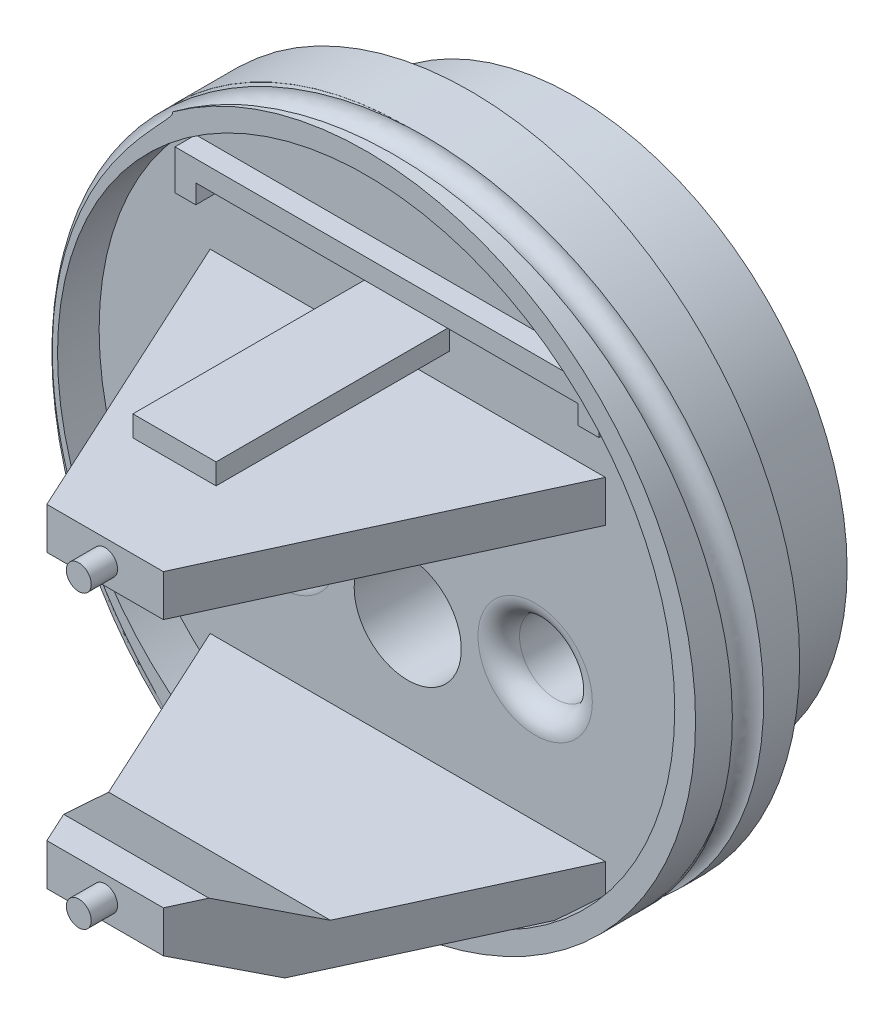
SolidWorks part; units mm, degrees
ref_plane "Front Plane" through (0, 0, 0) normal (0, 0, 1) x (1, 0, 0)
ref_plane "Top Plane" through (0, 0, 0) normal (0, 1, 0) x (1, 0, 0)
ref_plane "Right Plane" through (0, 0, 0) normal (1, 0, 0) x (0, 0, -1)
sketch "Sketch1" plane through (0, 0, 0) normal (0, 0, 1) x (1, 0, 0)
  circle A0 centre (0, 0) radius 31.685
extrude "Boss-Extrude1" add sketch "Sketch1" along normal blind 6
sketch "Sketch3" plane through (0, 0, 0) normal (0, 0, -1) x (-1, 0, 0)
  circle A0 centre (0, 0) radius 26.25
  dimension "D1" = 52.5
extrude "Boss-Extrude2" add sketch "Sketch3" along normal blind 10
sketch "Sketch2" plane through (0, 0, 0) normal (0, 0, -1) x (-1, 0, 0)
  line L0 (0, 0) -> (0, -50000) construction
  line L2 (-12.25, -7.3484) -> (-9, -7.3484) construction
  line L3 (12.25, -7.3484) -> (9, -7.3484) construction
  circle A0 centre (12.25, -7.3484) radius 3.25 construction
  circle A1 centre (0, -9.25) radius 4.755 construction
  circle A2 centre (0, 0) radius 17.535 construction
  circle A3 centre (0, 0) radius 31.685 construction
  circle A4 centre (-12.25, -7.3484) radius 3.25 construction
  circle A5 centre (-12.25, -7.3484) radius 3.5
  circle A6 centre (12.25, -7.3484) radius 3.5
  circle A7 centre (0, -9.25) radius 5.15
  point P11 (-9, -7.3484)
  point P12 (0, -4.495)
  point P14 (9, -7.3484)
  point P15 (0, -31.685)
  point P20 (0, -4.495)
  dimension "D1" = 14.15
  dimension "D2" = 18
  dimension "D3" = 6.5
  dimension "D4" = 9.51
  dimension "D6" = 7
  dimension "D7" = 7
  dimension "D8" = 10.3
  dimension "D5" = 27.19
extrude "Cut-Extrude1" cut sketch "Sketch2" against normal through all and the other way through all
sketch "Referance Lines Front" plane through (0, 0, 6) normal (0, 0, 1) x (1, 0, 0)
  line L0 (0, 0) -> (0, -50000) construction
  line L1 (0, 0) -> (50000, 0) construction
  line L2 (0, -9.25) -> (50000, -9.25) construction
  point P8 (0, -9.25)
  point P9 (0, 0)
sketch "Referance Line Right" plane through (0, 0, 0) normal (1, 0, 0) x (0, 0, -1)
  line L0 (-6, -9.25) -> (49994, -9.25) construction
sketch "Sketch6" plane through (0, 0, 6) normal (0, 0, 1) x (1, 0, 0)
  line L0 (0, 200000) -> (0, -250000) construction
  line L2 (-19, -24) -> (19, -24)
  line L3 (-19, 8) -> (19, 8)
  line L4 (-19, 8) -> (-19, 12)
  line L5 (-19, 12) -> (19, 12)
  line L6 (19, 8) -> (19, 12)
  line L7 (-19, 8) -> (19, 12) construction
  line L8 (-19, 12) -> (19, 8) construction
  line L9 (-19, -24) -> (-19, -20)
  line L10 (-19, -20) -> (19, -20)
  line L11 (19, -24) -> (19, -20)
  line L12 (-19, -24) -> (19, -20) construction
  line L13 (-19, -20) -> (19, -24) construction
  point P0 (0, 10)
  point P1 (0, -18)
  point P2 (0, -22)
  point P5 (0, 10)
  dimension "D1" = 19.25
  dimension "D2" = 8.75
  dimension "D3" = 4
  dimension "D4" = 38
  dimension "D5" = 4
  dimension "D6" = 38
  dimension "D7" = 4
extrude "Boss-Extrude3" add sketch "Sketch6" along normal blind 29.1
sketch "Sketch7" plane through (0, 12, 0) normal (0, 1, 0) x (1, 0, 0)
  line L2 (0, -35.1) -> (5.6, -35.1) construction
  line L3 (19, -35.1) -> (-19, -35.1) construction
  line L4 (0, -35.1) -> (-5.6, -35.1) construction
  line L5 (-19, -6) -> (-5.6, -35.1)
  line L6 (-5.6, -35.1) -> (-19, -35.1)
  line L7 (-19, -35.1) -> (-19, -6)
  line L8 (19, -6) -> (5.6, -35.1)
  line L9 (5.6, -35.1) -> (19, -35.1)
  line L10 (19, -35.1) -> (19, -6)
  dimension "D1" = 5.6
  dimension "D2" = 5.6
extrude "Cut-Extrude2" cut sketch "Sketch7" against normal through all
sketch "Sketch9" plane through (0, -20, 0) normal (0, 1, 0) x (1, 0, 0)
  line L0 (-6.9814, -32.1) -> (6.9814, -32.1)
  line L1 (-5.6, -35.1) -> (-19, -6) construction
  line L2 (19, -6) -> (5.6, -35.1) construction
  line L3 (6.9814, -32.1) -> (5.6, -35.1)
  line L4 (5.6, -35.1) -> (-5.6, -35.1)
  line L5 (-5.6, -35.1) -> (-6.9814, -32.1)
  dimension "D1" = 3
extrude "Boss-Extrude5" add sketch "Sketch9" along normal blind 4
chamfer "Chamfer1" distance 8 distance2 4 2 edges at (0, -20, 32.1) (0, -24, 35.1) first distance on face at (0, -20, 19.05) first distance on face at (0, -24, 20.55)
fillet "Fillet3" radius 2 2 edges at (8.75, -7.3484, 6) (-15.75, -7.3484, 6)
sketch "Sketch13" plane through (0, 0, 6) normal (0, 0, 1) x (1, 0, 0)
  line L0 (0, 200000) -> (0, -250000) construction
  line L1 (-4, 15) -> (4, 15)
  line L2 (-4, 15) -> (-4, 17)
  line L3 (-4, 17) -> (4, 17)
  line L4 (4, 15) -> (4, 17)
  line L5 (-4, 15) -> (4, 17) construction
  line L6 (-4, 17) -> (4, 15) construction
  line L7 (19, 12) -> (-19, 12) construction
  point P0 (0, 16)
  dimension "D1" = 8
  dimension "D2" = 2
  dimension "D3" = 4
extrude "Boss-Extrude8" add sketch "Sketch13" along normal blind 22.43
sketch "Sketch14" plane through (0, 0, 6) normal (0, 0, 1) x (1, 0, 0)
  line L0 (0, 200000) -> (0, -250000) construction
  line L1 (-18.38, 18.83) -> (18.38, 18.83)
  line L3 (-18.38, 20.83) -> (18.38, 20.83)
  line L5 (-18.38, 18.83) -> (18.38, 20.83) construction
  line L6 (-18.38, 20.83) -> (18.38, 18.83) construction
  line L7 (4, 17) -> (-4, 17) construction
  line L8 (-4, 17) -> (-50004, 17) construction
  line L9 (-18.38, 18.83) -> (-18.38, 17)
  line L10 (-18.38, 17) -> (-20.38, 17)
  line L11 (-20.38, 17) -> (-20.38, 20.83)
  line L12 (-20.38, 20.83) -> (-18.38, 20.83)
  line L13 (0, 0) -> (0, 50000) construction
  line L14 (20.38, 17) -> (20.38, 20.83)
  line L15 (18.38, 17) -> (20.38, 17)
  line L16 (18.38, 18.83) -> (18.38, 17)
  line L17 (20.38, 20.83) -> (18.38, 20.83)
  point P0 (0, 19.83)
  dimension "D1" = 2
  dimension "D2" = 36.76
  dimension "D3" = 1.83
  dimension "D4" = 2
extrude "Boss-Extrude9" add sketch "Sketch14" along normal blind 2
sketch "Sketch17" plane through (0, 0, 35.1) normal (0, 0, 1) x (1, 0, 0)
  line L0 (0, 200000) -> (0, -250000) construction
  line L3 (-5.6, 12) -> (5.6, 8) construction
  line L4 (5.6, -16) -> (-5.6, -20) construction
  circle A0 centre (0, 10) radius 1.2
  circle A1 centre (0, -18) radius 1.2
extrude "Boss-Extrude10" add sketch "Sketch17" along normal blind 2.53
sketch "Sketch18" plane through (0, 0, 6) normal (0, 0, 1) x (1, 0, 0)
  circle A0 centre (0, 0) radius 31.6751
  circle A1 centre (0, 0) radius 29.6751
  dimension "D1" = 2
extrude "Boss-Extrude11" add sketch "Sketch18" along normal blind 4
sketch "Sketch21" plane through (0, 0, -10) normal (0, 0, -1) x (-1, 0, 0)
  circle A0 centre (0, 0) radius 31.685
curve "Helix/Spiral2" pitch 10 height 30 radius 31.685 centre (0, 0, -10) axis (0, 0, 1) start towards (-1, 0, 0)
sketch "Sketch20" plane through (0, 0, 0) normal (0, 1, 0) x (1, 0, 0)
  circle A0 centre (-31.6751, -10) radius 1.5
  dimension "D1" = 3
sweep "Cut-Sweep1" cut profiles "Sketch20" path "Helix/Spiral2" align with end faces yes
